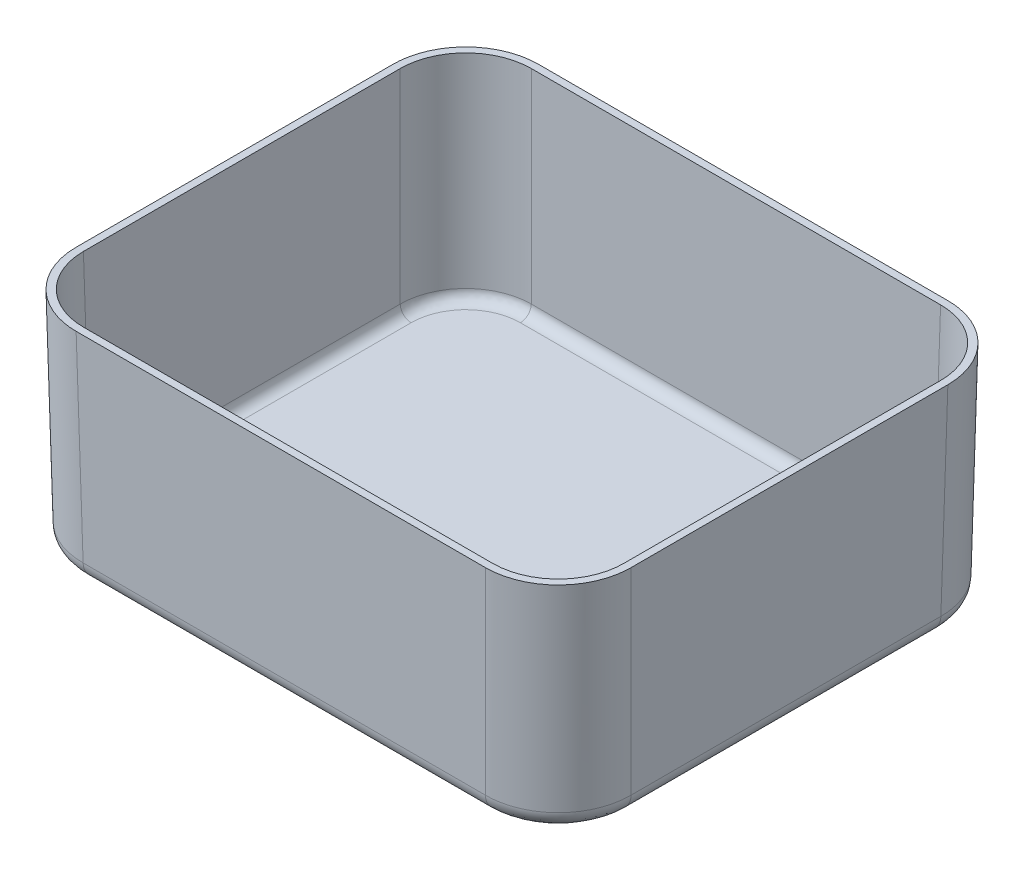
SolidWorks part; units mm, degrees
ref_plane "Front Plane" through (0, 0, 0) normal (0, 0, 1) x (1, 0, 0)
ref_plane "Top Plane" through (0, 0, 0) normal (0, 1, 0) x (1, 0, 0)
ref_plane "Right Plane" through (0, 0, 0) normal (1, 0, 0) x (0, 0, -1)
sketch "Sketch1" plane through (0, 0, 0) normal (0, 1, 0) x (1, 0, 0)
  line L1 (-76.2, 63.5) -> (76.2, 63.5)
  line L2 (-76.2, 63.5) -> (-76.2, -63.5)
  line L3 (-76.2, -63.5) -> (76.2, -63.5)
  line L4 (76.2, 63.5) -> (76.2, -63.5)
  line L5 (-76.2, 63.5) -> (76.2, -63.5) construction
  line L6 (-76.2, -63.5) -> (76.2, 63.5) construction
  point P0 (0, 0)
  dimension "D1" = 127
  dimension "D2" = 152.4
extrude "Boss-Extrude1" add sketch "Sketch1" against normal blind 60 draft 1
fillet "Fillet1" radius 20 4 edges at (-75.6763, -30, -62.9763) (-75.6763, -30, 62.9763) (75.6763, -30, 62.9763) (75.6763, -30, -62.9763)
fillet "Fillet2" radius 5 8 edges at (-69.2961, -60, 56.5961) (0, -60, 62.4527) (69.2961, -60, 56.5961) (75.1527, -60, 0) (69.2961, -60, -56.5961) (0, -60, -62.4527) (-69.2961, -60, -56.5961) (-75.1527, -60, 0)
shell "Shell1" thickness 2 removed face at (0, 0, 0)
